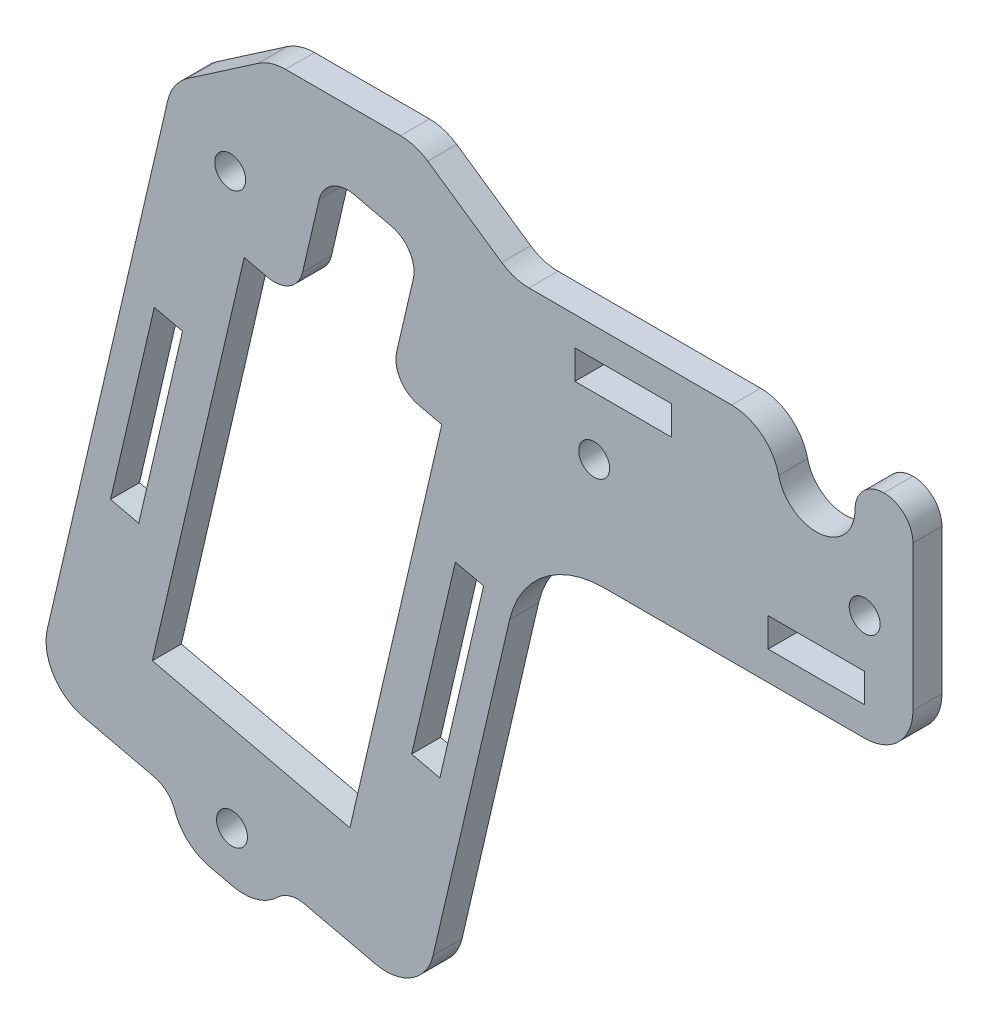
SolidWorks part; units mm, degrees
material "MDF"
ref_plane "Plano frontal" through (0, 0, 0) normal (0, 0, 1) x (1, 0, 0)
ref_plane "Plano superior" through (0, 0, 0) normal (0, 1, 0) x (1, 0, 0)
ref_plane "Plano direito" through (0, 0, 0) normal (1, 0, 0) x (0, 0, -1)
sketch "Esboço1" plane through (0, 0, 0) normal (0, 0, 1) x (1, 0, 0)
  line L0 (0, 20) -> (0, 0) construction
  line L5 (10, 16) -> (13, 16) construction
  line L6 (13, 6) -> (13, 16) construction
  line L15 (5, 11) -> (-10, 11) construction
  line L16 (10, 6) -> (13, 6) construction
  line L21 (-10, 6) -> (-13, 6) construction
  line L22 (-10, 6) -> (-10, 16) construction
  line L27 (-10, 16) -> (-13, 16) construction
  line L28 (-13, 6) -> (-13, 16) construction
  line L29 (-10, 6) -> (-13, 16) construction
  line L30 (-10, 16) -> (-13, 6) construction
  line L35 (10, 6) -> (10, 16) construction
  line L36 (18, 0) -> (18, 23)
  line L37 (18, 23) -> (-66.701, 23)
  line L43 (-29.9553, 0) -> (18, 0)
  line L61 (-68.7379, -29.9136) -> (-59.2257, 10.995)
  line L66 (-59.2257, 10.995) -> (-38.7714, 6.2389)
  line L67 (-38.7714, 6.2389) -> (-48.2836, -34.6697)
  line L68 (-48.2836, -34.6697) -> (-68.7379, -29.9136)
  line L69 (-63.9818, -9.4593) -> (-43.5275, -14.2154) construction
  line L74 (-48.9985, 8.617) -> (-58.5107, -32.2917) construction
  line L75 (-61.7051, 0.3321) -> (-41.2508, -4.424) construction
  line L80 (-38.7714, 6.2389) -> (-38.7714, -27.2218) construction
  line L85 (0, 20) -> (-15.8727, -48.263) construction
  line L86 (5, 3) -> (-5, 3)
  line L87 (-66.701, 23) -> (-80.7429, -37.389)
  line L88 (-80.7429, -37.389) -> (-40.8082, -46.6747)
  line L89 (-40.8082, -46.6747) -> (-29.9553, 0)
  line L93 (-65.6456, -40.8994) -> (-66.4949, -44.552)
  line L94 (-66.4949, -44.552) -> (-56.7548, -46.8168)
  line L95 (-55.9055, -43.1642) -> (-56.7548, -46.8168)
  line L96 (-47.0168, 17.1396) -> (-48.1492, 12.2695) construction
  line L97 (-48.1492, 12.2695) -> (-53.0193, 13.4019) construction
  line L98 (5, 3) -> (5, 6)
  line L99 (5, 6) -> (-5, 6)
  line L100 (-5, 3) -> (-5, 6)
  line L101 (0, 6) -> (0, 0) construction
  line L102 (5, 4.5) -> (-5, 4.5) construction
  line L103 (10, 0) -> (10, 23)
  line L104 (-73.0647, -17.6141) -> (-70.1427, -18.2935)
  line L105 (-70.1427, -18.2935) -> (-65.6131, 1.1868)
  line L106 (-65.6131, 1.1868) -> (-68.5351, 1.8662)
  line L107 (-38.9742, -25.5409) -> (-41.8962, -24.8615)
  line L108 (-37.3666, -5.3812) -> (-34.4446, -6.0606)
  line L109 (-41.8962, -24.8615) -> (-37.3666, -5.3812)
  line L115 (-53.8686, 9.7494) -> (-50.7875, 23)
  line L116 (-50.7875, 23) -> (-41.0474, 20.7352)
  line L117 (-25, 17) -> (-15, 17)
  line L118 (-25, 17) -> (-25, 20)
  line L119 (-25, 20) -> (-15, 20)
  line L120 (-15, 17) -> (-15, 20)
  line L121 (-20, 20) -> (-20, 17) construction
  line L122 (-25, 18.5) -> (-15, 18.5) construction
  line L123 (-68.5351, 1.8662) -> (-73.0647, -17.6141)
  line L124 (-38.9742, -25.5409) -> (-34.4446, -6.0606)
  line L125 (-41.0474, 20.7352) -> (-44.1285, 7.4846)
  line L126 (-66.701, 23) -> (-56.4985, 30)
  line L127 (-56.4985, 30) -> (-41.4985, 30)
  line L128 (-41.4985, 30) -> (-31.296, 23)
  circle A0 centre (0, 20) radius 7.5 construction
  circle A1 centre (5, 11) radius 1.6
  circle A2 centre (-10, 11) radius 1.6 construction
  circle A8 centre (-64.2301, -34.8118) radius 1.6 construction
  circle A9 centre (-54.49, -37.0766) radius 1.6 construction
  circle A10 centre (-43.2792, 11.1371) radius 1.6 construction
  circle A11 centre (-53.0193, 13.4019) radius 1.6 construction
  circle A12 centre (-47.0168, 17.1396) radius 1.6 construction
  circle A15 centre (-60.4925, -40.8143) radius 1.6
  circle A16 centre (-23, 11) radius 1.6
  circle A17 centre (-60.6769, 18) radius 1.6
  circle A18 centre (0, 20) radius 4
  point P0 (0, 20)
  point P13 (-11.5, 11)
  point P39 (-51.4779, -2.046)
  point P49 (0, 4.5)
  point P56 (-67.8779, -8.5534)
  point P61 (0, 11)
  point P72 (-20, 18.5)
  point P82 (-45.9175, 21.8676)
  point P85 (-48.9985, 30)
  point P88 (0, 0)
  point P89 (-41.0474, 30)
  point P90 (0, 0)
  point P91 (-25, 18.0656)
  point P92 (-5, 4.3257)
  dimension "D1" = 15
  dimension "D3" = 3.2
  dimension "D11" = 14.6974
  dimension "D12" = 56
  dimension "D9" = 49.5
  dimension "D30" = 5
  dimension "D31" = 5
  dimension "D28" = 10
  dimension "D35" = 7
  dimension "D36" = 5
  dimension "D25" = 8
  dimension "D2" = 15
  dimension "D4" = 5
  dimension "D5" = 21
  dimension "D6" = 10
  dimension "D7" = 3
  dimension "D8" = 42
  dimension "D10" = 10
  dimension "D13" = 20
  dimension "D14" = 5
  dimension "D15" = 10
  dimension "D16" = 10
  dimension "D17" = 6
  dimension "D18" = 5
  dimension "D19" = 7
  dimension "D20" = 5
  dimension "D21" = 13.09
  dimension "D22" = 10
  dimension "D23" = 10
  dimension "D24" = 10
  dimension "D26" = 3
  dimension "D27" = 20
  dimension "D29" = 10
  dimension "D32" = 7
  dimension "D33" = 5
  dimension "D34" = 4
  dimension "D37" = 15
  dimension "D38" = 3
  dimension "D39" = 3
extrude "Ressalto-extrusão1" add sketch "Esboço1" along normal blind 3 contours L6 A0 | L88 A15 L89 L107 L109 L108 L43 L37 L87 L106 L105 L104 A16 A12 A1 L67 L68 L61 L66 L21 L28 L27 L22 L86 L100 L99 L98 | L88 A15 L93 L94 L95 | L128 L127 L126 L37 region at (-38.7159, -3.6281, 0) region at (-61.2053, -43.8799, 0) region at (-48.9985, 26.0277, 0)
fillet "Filete1" radius 5 3 edges at (-40.8082, -46.6747, 1.5) (-80.7429, -37.389, 1.5) (10, 0, 1.5)
fillet "Filete3" radius 3 8 edges at (-65.6456, -40.8994, 1.5) (-55.9055, -43.1642, 1.5) (2.6458, 23, 1.5) (10, 23, 1.5) (-50.7875, 23, 1.5) (-41.0474, 20.7352, 1.5) (-44.1285, 7.4846, 1.5) (-53.8686, 9.7494, 1.5)
fillet "Filete4" radius 10 1 edges at (-29.9553, 0, 1.5)
fillet "Filete2" radius 5 7 edges at (-2.6458, 23, 1.5) (-56.7548, -46.8168, 1.5) (-66.4949, -44.552, 1.5) (-31.296, 23, 1.5) (-41.4985, 30, 1.5) (-56.4985, 30, 1.5) (-66.701, 23, 1.5)
